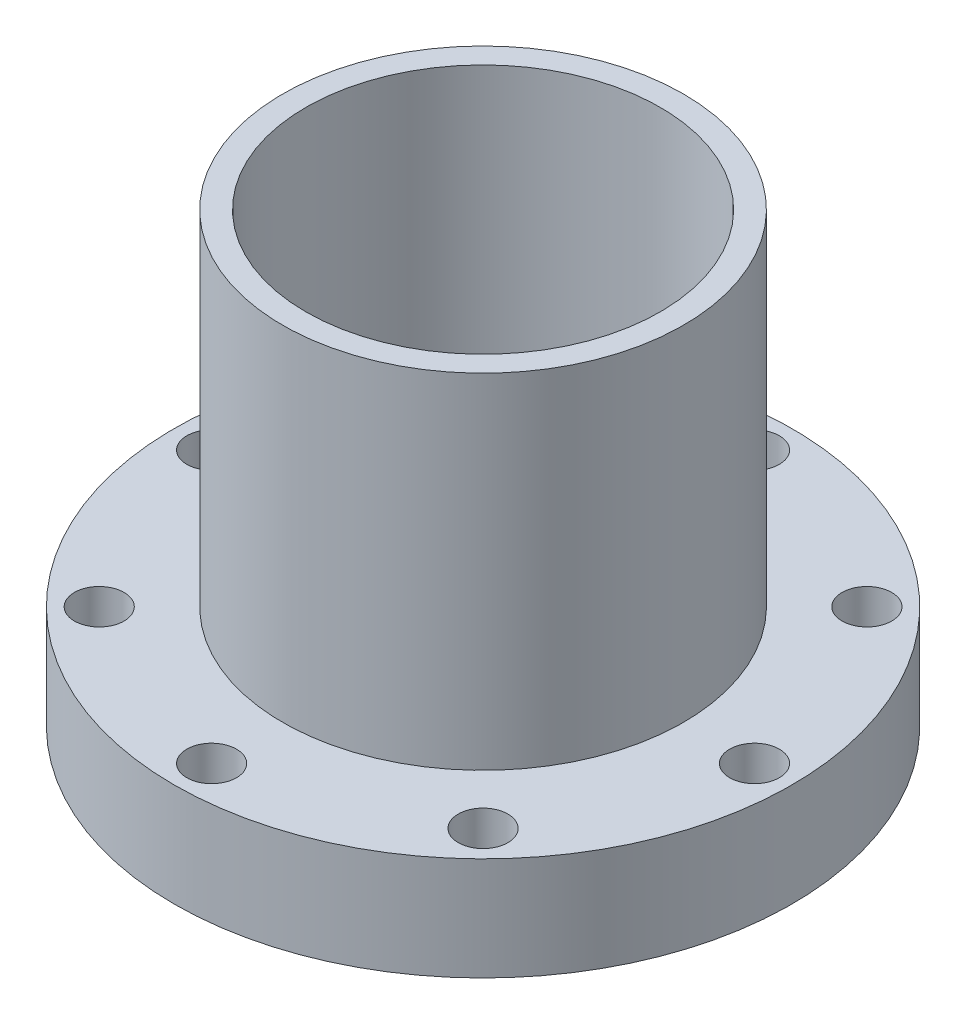
SolidWorks part; units mm, degrees
ref_plane "Front Plane" through (0, 0, 0) normal (0, 0, 1) x (1, 0, 0)
ref_plane "Top Plane" through (0, 0, 0) normal (0, 1, 0) x (1, 0, 0)
ref_plane "Right Plane" through (0, 0, 0) normal (1, 0, 0) x (0, 0, -1)
sketch "Sketch1" plane through (0, 0, 0) normal (0, 1, 0) x (1, 0, 0)
  circle A0 centre (0, 0) radius 34.036
extrude "Extrude1" add sketch "Sketch1" along normal blind 58.42
sketch "Sketch2" plane through (0, 0, 0) normal (0, 1, 0) x (1, 0, 0)
  circle A0 centre (0, 0) radius 52.451
  dimension "D1" = 104.902
extrude "Extrude2" add sketch "Sketch2" against normal blind 17.526
sketch "Sketch3" plane through (0, 0, 0) normal (0, 1, 0) x (1, 0, 0)
  circle A0 centre (0, 0) radius 30.099
  dimension "D1" = 60.198
extrude "Cut-Extrude1" cut sketch "Sketch3" against normal through all and the other way through all
sketch "Sketch4" plane through (0, 0, 0) normal (0, 1, 0) x (1, 0, 0)
  circle A0 centre (0, 46.101) radius 4.2164
  dimension "D1" = 8.4328
extrude "Cut-Extrude2" cut sketch "Sketch4" against normal blind 17.526
ref_axis "Axis1" through (0, 58.677, 0) along (0, -1, 0)
pattern_circular "CirPattern1" count 8 over 360 about axis through (0, 58.677, 0) along (0, -1, 0) of "Cut-Extrude2"
ref_plane "Plane1" through (0, -17.526, 0) normal (0, -1, 0) x (1, 0, 0)
sketch "Sketch9" plane through (0, -17.526, 0) normal (0, -1, 0) x (1, 0, 0)
  line L0 (0, 0) -> (32.5983, 32.5983)
  line L1 (0, 0) -> (13.3652, 32.2665)
  dimension "D1" = 34.925
  dimension "D2" = 22.5
hole_wizard "1/4-20 Tapped Hole2" positions "3DSketch3" profile "Sketch10" tap size "1/4-20" standard "Ansi Inch"
sketch3d "3DSketch3"
  point P0 (13.3652, -17.526, 32.2665)
sketch "Sketch10" plane through (13.3652, -17.526, 32.2665) normal (1, 0, 0) x (0, 0, -1)
  line L0 (0, 0) -> (0, 15.5038)
  line L1 (0, 15.5038) -> (2.5527, 13.97)
  line L2 (2.5527, 13.97) -> (2.5527, 0)
  line L5 (2.5527, 0) -> (0, 0)
  line L10 (0, 15.5038) -> (-2.5527, 13.97) construction
  line L11 (0, -6.35) -> (0, 107.95) construction
  dimension "Tap Drill Dia." = 5.1054
  dimension "Tap Drill Depth" = 13.97
  dimension "Drill Angle" = 118
cosmetic thread "Hole Thread2" parameters "D1"=12.7, "D2"=6.35
pattern_circular "CirPattern3" count 8 over 360 about axis through (0, 58.677, 0) along (0, -1, 0) of "1/4-20 Tapped Hole2"
ref_plane "Plane2" through (0, 58.42, 0) normal (0, 1, 0) x (-1, 0, 0)
sketch "Sketch11" plane through (0, 58.42, 0) normal (0, 1, 0) x (-1, 0, 0)
  point P0 (0, 0)
sketch "Sketch12" plane through (0, 0, 0) normal (0, 0, 1) x (1, 0, 0)
  line L0 (0, 0) -> (0, 91.8051)
